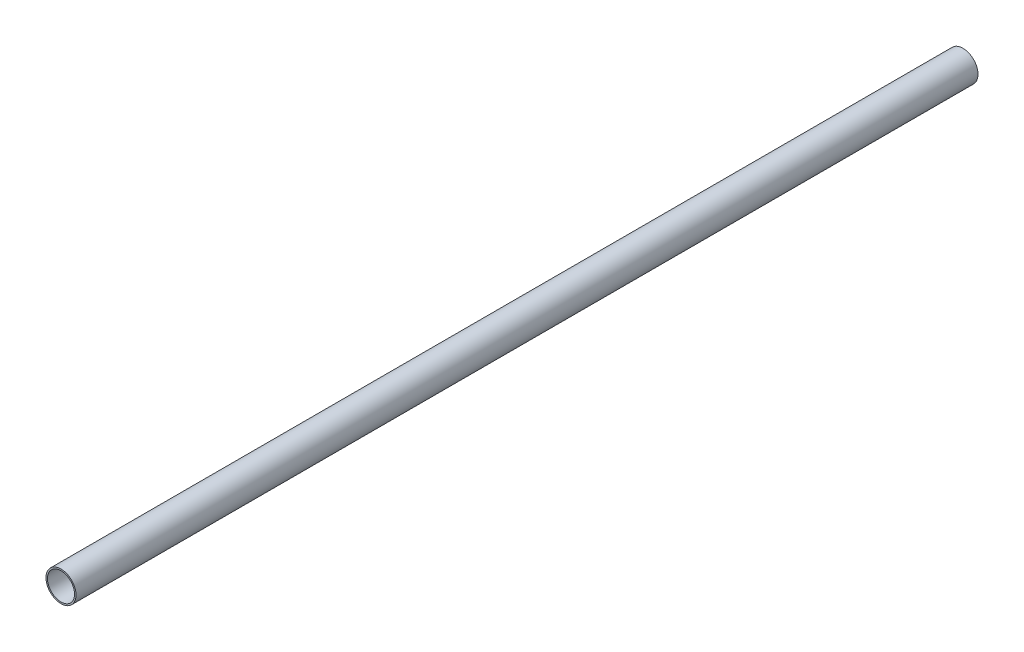
SolidWorks part; units mm, degrees
material "Carbon Fiber Tube - UD Approx"
ref_plane "Front Plane" through (0, 0, 0) normal (0, 0, 1) x (1, 0, 0)
ref_plane "Top Plane" through (0, 0, 0) normal (0, 1, 0) x (1, 0, 0)
ref_plane "Right Plane" through (0, 0, 0) normal (1, 0, 0) x (0, 0, -1)
sketch "Sketch1" plane through (0, 0, 0) normal (0, 0, 1) x (1, 0, 0)
  circle A0 centre (0, 0) radius 10
  circle A1 centre (0, 0) radius 9
  dimension "D1" = 20
  dimension "D2" = 18
extrude "Boss-Extrude1" add sketch "Sketch1" along normal blind 600
